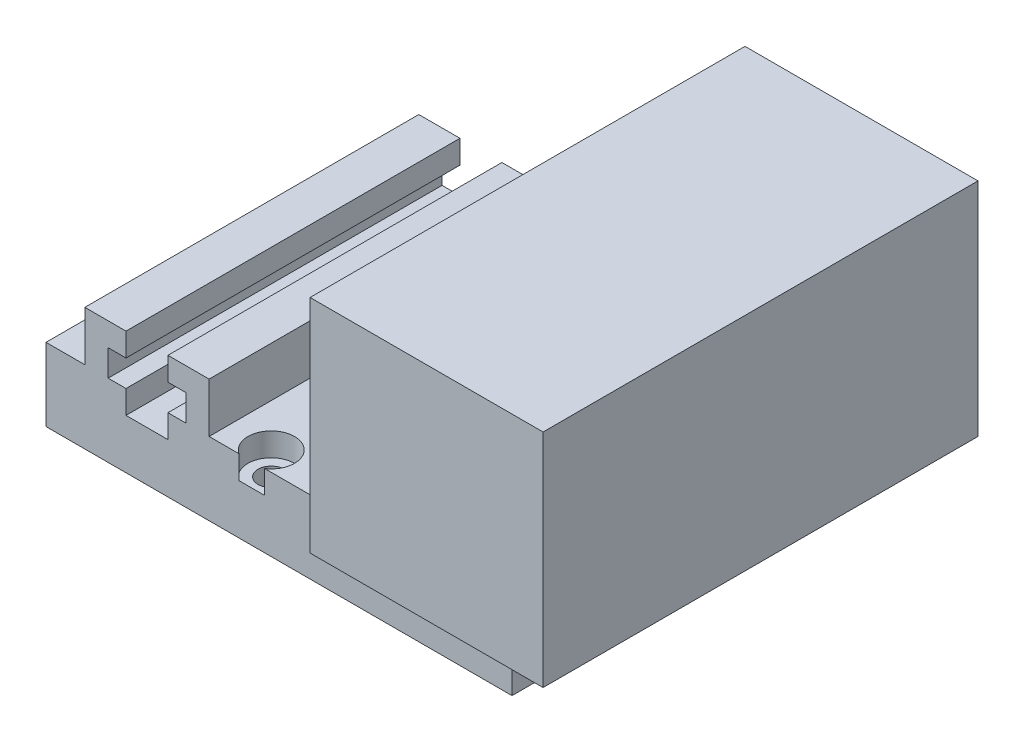
SolidWorks part; units mm, degrees
ref_plane "Front Plane" through (0, 0, 0) normal (0, 0, 1) x (1, 0, 0)
ref_plane "Top Plane" through (0, 0, 0) normal (0, 1, 0) x (1, 0, 0)
ref_plane "Right Plane" through (0, 0, 0) normal (1, 0, 0) x (0, 0, -1)
sketch "Sketch1" plane through (0, 0, 0) normal (0, 1, 0) x (1, 0, 0)
  line L1 (0, 0) -> (60, 0)
  line L2 (0, 0) -> (0, 43)
  line L3 (0, 43) -> (60, 43)
  line L4 (60, 0) -> (60, 43)
  dimension "D1" = 60
  dimension "D2" = 43
extrude "Boss-Extrude1" add sketch "Sketch1" along normal blind 5
sketch "Sketch2" plane through (0, 0, 0) normal (0, -1, 0) x (-1, 0, 0)
  line L0 (-60, 0) -> (-60, 43) construction
  line L1 (0, 0) -> (-60, 0)
  line L2 (0, 0) -> (0, 5)
  line L3 (0, 5) -> (-60, 5)
  line L4 (-60, 0) -> (-60, 5)
  line L6 (0, 43) -> (0, 0) construction
  line L7 (0, 43) -> (-60, 43)
  line L8 (0, 43) -> (0, 38)
  line L9 (0, 38) -> (-60, 38)
  line L10 (-60, 43) -> (-60, 38)
  dimension "D1" = 5
extrude "Boss-Extrude2" add sketch "Sketch2" along normal blind 4.4
sketch "Sketch3" plane through (0, 5, 0) normal (0, 1, 0) x (1, 0, 0)
  line L0 (60, 43) -> (0, 43) construction
  line L1 (5, 43) -> (8, 43)
  line L2 (5, 43) -> (5, 0)
  line L3 (5, 0) -> (8, 0)
  line L4 (8, 43) -> (8, 0)
  line L5 (0, 0) -> (60, 0) construction
  line L6 (0, 43) -> (0, 0) construction
  line L7 (18, 43) -> (21, 43)
  line L8 (18, 43) -> (18, 0)
  line L9 (18, 0) -> (21, 0)
  line L10 (21, 43) -> (21, 0)
  dimension "D1" = 3
  dimension "D2" = 10
  dimension "D3" = 5
extrude "Boss-Extrude3" add sketch "Sketch3" along normal blind 6.4
sketch "Sketch4" plane through (8, 0, 0) normal (1, 0, 0) x (0, 0, -1)
  line L0 (43, 11.4) -> (43, 5) construction
  line L1 (0, 11.4) -> (43, 11.4)
  line L2 (0, 11.4) -> (0, 8.4)
  line L3 (0, 8.4) -> (43, 8.4)
  line L4 (43, 11.4) -> (43, 8.4)
  dimension "D1" = 3
extrude "Boss-Extrude4" add sketch "Sketch4" along normal blind 2.3
ref_plane "Plane1" through (13, 0, 0) normal (1, 0, 0) x (0, 0, -1)
mirror "Mirror1" about plane through (13, 0, 0) normal (1, 0, 0) of "Boss-Extrude4"
sketch "Sketch5" plane through (0, 5, 0) normal (0, 1, 0) x (1, 0, 0)
  line L1 (40.5, 49.5) -> (70.5, 49.5)
  line L2 (40.5, 49.5) -> (40.5, -6.5)
  line L3 (40.5, -6.5) -> (70.5, -6.5)
  line L4 (70.5, 49.5) -> (70.5, -6.5)
  line L6 (13, -1.87) -> (13, 1.87) construction
  line L7 (60, 0) -> (60, 43) construction
  line L8 (60, 21.5) -> (70.5, 21.5) construction
  dimension "D1" = 30
  dimension "D2" = 27.5
  dimension "D3" = 56
extrude "Boss-Extrude5" add sketch "Sketch5" along normal blind 28.5
sketch "Sketch6" plane through (40.5, 0, 0) normal (-1, 0, 0) x (0, 0, 1)
  line L0 (-43, 5) -> (0, 5) construction
  line L1 (-41.7, 30.7) -> (-1.3, 30.7)
  line L2 (-41.7, 30.7) -> (-41.7, 10.3)
  line L3 (-41.7, 10.3) -> (-1.3, 10.3)
  line L4 (-1.3, 30.7) -> (-1.3, 10.3)
  line L5 (-49.5, 33.5) -> (6.5, 33.5) construction
  line L6 (-21.5, 30.7) -> (-21.5, 33.5) construction
  point P4 (-41.7, 20.5)
  dimension "D1" = 20.4
  dimension "D2" = 15.5
  dimension "D3" = 40.4
extrude "Cut-Extrude1" cut sketch "Sketch6" against normal blind 28
sketch "Sketch7" plane through (40.5, 0, 0) normal (-1, 0, 0) x (0, 0, 1)
  line L0 (-46, 25.5) -> (3, 25.5) construction
  line L1 (-49.5, 33.5) -> (6.5, 33.5) construction
  line L2 (-21.5, 25.5) -> (-21.5, 33.5) construction
  line L3 (3, 25.5) -> (3, 15.5)
  line L4 (3, 20.5) -> (-1.3, 20.5) construction
  line L5 (-1.3, 10.3) -> (-1.3, 30.7) construction
  circle A0 centre (-46, 25.5) radius 1.05
  circle A1 centre (-46, 15.5) radius 1.05
  circle A2 centre (3, 25.5) radius 1.05
  circle A3 centre (3, 15.5) radius 1.05
  dimension "D1" = 2.1
  dimension "D2" = 10
  dimension "D3" = 49
extrude "Cut-Extrude2" cut sketch "Sketch7" against normal blind 25 contours A0 | A1 | A3 | A2 region at (40.5, 16.2215, 3.7215) region at (40.5, 26.2215, 2.2785) region at (40.5, 25.5, -46) region at (40.5, 15.5, -46)
sketch "Sketch8" plane through (0, 0, 0) normal (0, 0, 1) x (1, 0, 0)
  line L0 (8, 5) -> (18, 5) construction
  line L1 (10.3, 5) -> (15.7, 5)
  line L2 (10.3, 5) -> (10.3, 2)
  line L3 (10.3, 2) -> (15.7, 2)
  line L4 (15.7, 5) -> (15.7, 2)
  line L5 (13, -1.87) -> (13, 1.87) construction
  point P6 (13, 5)
  dimension "D1" = 3
  dimension "D2" = 5.4
extrude "Cut-Extrude3" cut sketch "Sketch8" against normal offset from surface (33 mm away) 10 up to face at (18.6176, 6.2, -43)
sketch "Sketch9" plane through (0, 5, 0) normal (0, 1, 0) x (1, 0, 0)
  line L0 (40.5, 43) -> (21, 43) construction
  line L1 (40.5, 49.5) -> (40.5, -6.5) construction
  line L2 (0, 21.5) -> (50000, 21.5) construction
  line L3 (0, 43) -> (0, 0) construction
  circle A0 centre (26.5, 40.5) radius 1.7
  circle A1 centre (36.5, 40.5) radius 1.7
  circle A2 centre (36.5, 2.5) radius 1.7
  circle A3 centre (26.5, 2.5) radius 1.7
  point P12 (0, 21.5)
  dimension "D1" = 3.4
  dimension "D2" = 10
  dimension "D3" = 2.5
  dimension "D4" = 4
extrude "Cut-Extrude4" cut sketch "Sketch9" against normal up to next
sketch "Sketch10" plane through (0, 5, 0) normal (0, 1, 0) x (1, 0, 0)
  circle A0 centre (26.5, 40.5) radius 3
  circle A1 centre (36.5, 40.5) radius 3
  circle A2 centre (26.5, 2.5) radius 3
  circle A3 centre (36.5, 2.5) radius 3
  dimension "D1" = 6
extrude "Cut-Extrude5" cut sketch "Sketch10" against normal blind 3
sketch "Sketch11" plane through (40.5, 0, 0) normal (-1, 0, 0) x (0, 0, 1)
  line L0 (-49.5, 33.5) -> (-49.5, 5) construction
  line L1 (-49.5, 24.25) -> (-41.7, 24.25)
  line L2 (-49.5, 24.25) -> (-49.5, 16.75)
  line L3 (-49.5, 16.75) -> (-41.7, 16.75)
  line L4 (-41.7, 24.25) -> (-41.7, 16.75)
  line L5 (-41.7, 30.7) -> (-41.7, 10.3) construction
  point P8 (-41.7, 20.5)
  point P9 (-49.5, 20.5)
  dimension "D1" = 7.5
extrude "Cut-Extrude6" cut sketch "Sketch11" against normal up to surface (28 mm away) up to face at (68.5, 20.5, -21.5)
